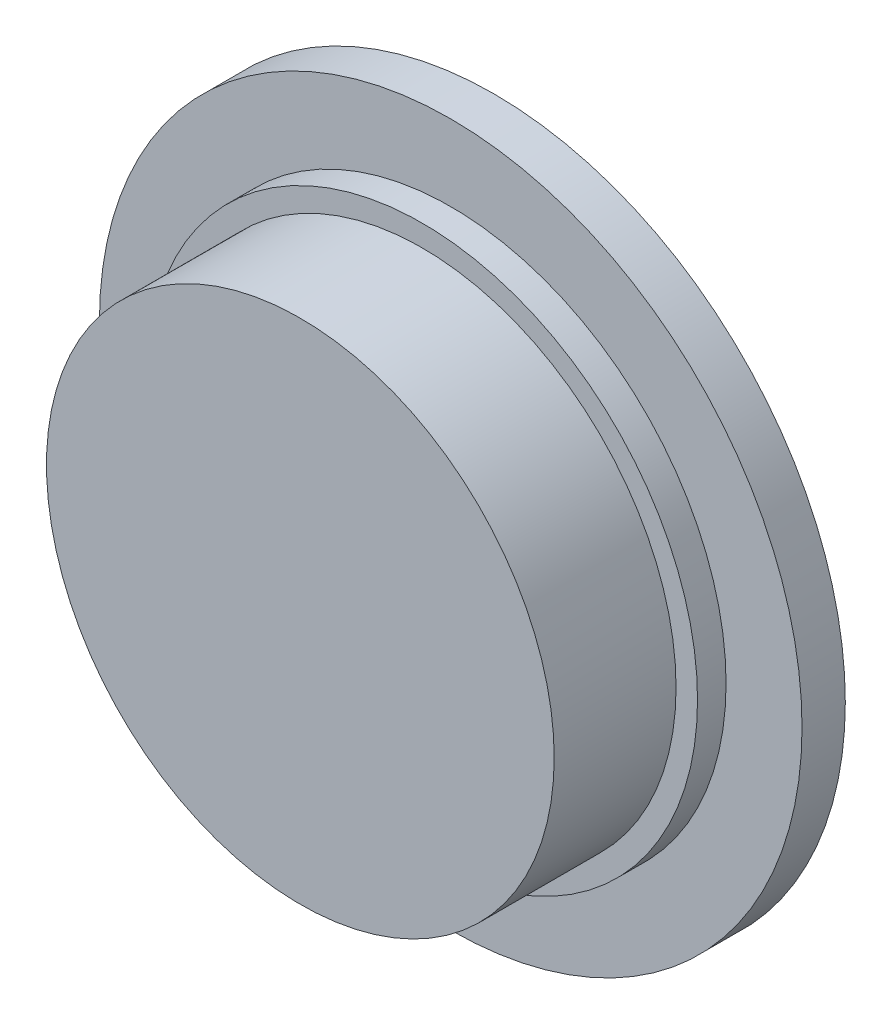
SolidWorks part; units mm, degrees
ref_plane "Front Plane" through (0, 0, 0) normal (0, 0, 1) x (1, 0, 0)
ref_plane "Top Plane" through (0, 0, 0) normal (0, 1, 0) x (1, 0, 0)
ref_plane "Right Plane" through (0, 0, 0) normal (1, 0, 0) x (0, 0, -1)
sketch "Sketch1" plane through (0, 0, 0) normal (1, 0, 0) x (0, 0, -1)
  line L0 (0, 9.5) -> (0, 7.4456)
  line L1 (224.503, 127.5793) -> (224.503, 46.6019) construction
  line L2 (0, 9.5) -> (1.1704, 9.5)
  line L3 (-42.4232, 0) -> (5.8689, 0) construction
  line L4 (-0.7715, 7.4456) -> (0, 7.4456)
  line L5 (-0.7715, 7.4456) -> (-0.7715, 6.8648)
  line L6 (-0.7715, 6.8648) -> (-4.0664, 6.8648)
  line L7 (-4.0664, 6.8648) -> (-4.0664, 8.4843)
  line L8 (-4.0664, 8.4843) -> (-4.9756, 9.5462)
  line L9 (-4.9756, 9.5462) -> (-7.0642, 9.5462)
  line L10 (-7.0642, 9.5462) -> (-7.7679, 10.9542)
  line L11 (-7.7679, 10.9542) -> (-9.164, 10.9542)
  line L12 (-9.164, 10.9542) -> (-9.9459, 9.5462)
  line L13 (-9.9459, 9.5462) -> (-9.9459, 8)
  line L14 (-9.9459, 8) -> (-19.8961, 8)
  line L15 (-19.8961, 8) -> (-20.5664, 7.426)
  line L16 (-20.5664, 7.426) -> (-23.1214, 7.426)
  line L17 (-23.1214, 7.426) -> (-23.6826, 6.8648)
  line L18 (-23.6826, 6.8648) -> (-23.6826, 6.3835)
  line L19 (-23.6826, 6.3835) -> (-27.0134, 6.3835)
  line L20 (-27.0134, 6.3835) -> (-27.0134, 5.4642)
  line L21 (-27.0134, 5.4642) -> (-31.932, 5.4642)
  line L22 (-31.932, 5.4642) -> (-31.932, 1.4475)
  line L23 (-31.932, 1.4475) -> (-38.1113, 1.4475)
  line L24 (-38.1113, 1.4475) -> (-38.932, 1.0374)
  line L25 (-38.932, 1.0374) -> (-38.932, 0)
  line L26 (-38.932, 0) -> (2.9336, 0)
  arc A0 (1.1704, 9.5) -> (2.9336, 0) centre (-23.54, 0) cw
  point P4 (0, 0)
  dimension "D1" = 7
  dimension "D2" = 16.5
  dimension "D3" = 19
  dimension "D4" = 16
  dimension "D5" = 7
revolve "Revolve2" add sketch "Sketch1" angle 360 about L26
split "Split1" bodies to split 101 resulting bodies 103 104 split by face at (8.4843, 0, 4.0664)
sketch "Sketch6" plane through (0, 0, 4.0664) normal (0, 0, -1) x (-1, 0, 0)
  circle A0 centre (0, 0) radius 6.8648
extrude "Cut-Extrude2" cut sketch "Sketch6" against normal blind 3.3
sketch "Sketch5" plane through (0, 0, 4.0664) normal (0, 0, -1) x (-1, 0, 0)
  circle A0 centre (0, 0) radius 15.7026
extrude "Cut-Extrude3" cut sketch "Sketch5" against normal blind 40
